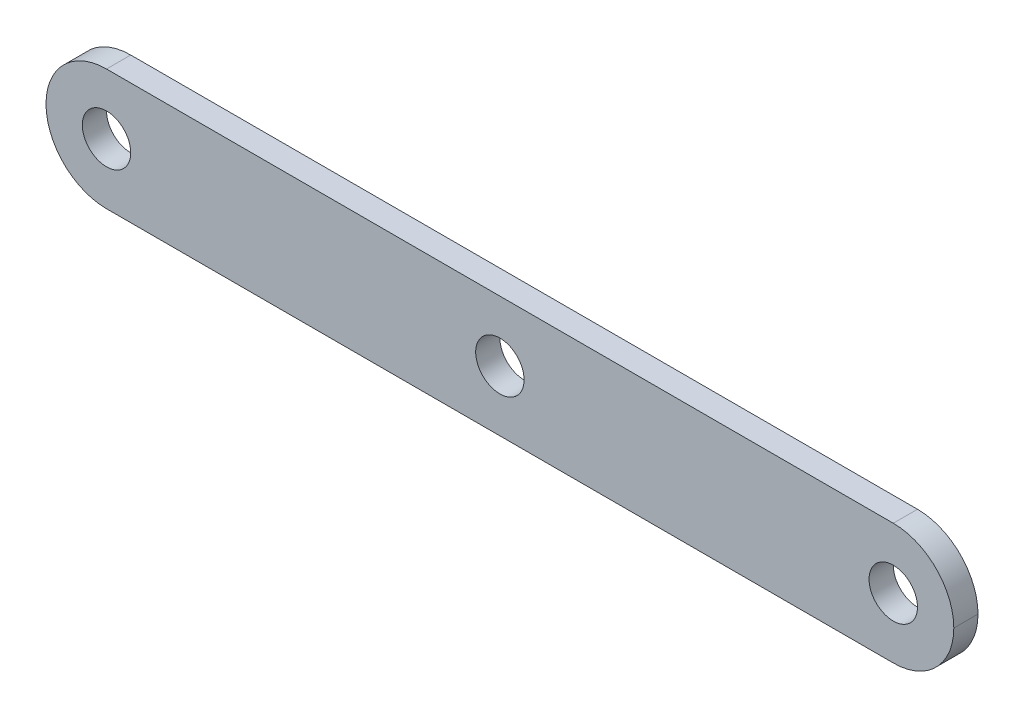
SolidWorks part; units mm, degrees
material "Thornel Mat VMA"
ref_plane "前视基准面" through (0, 0, 0) normal (0, 0, 1) x (1, 0, 0)
ref_plane "上视基准面" through (0, 0, 0) normal (0, 1, 0) x (1, 0, 0)
ref_plane "右视基准面" through (0, 0, 0) normal (1, 0, 0) x (0, 0, -1)
sketch "草图1" plane through (0, 0, 0) normal (0, 0, 1) x (1, 0, 0)
  line L1 (-37.5, -5) -> (37.5, -5)
  line L2 (-37.5, -5) -> (-37.5, 5)
  line L3 (-37.5, 5) -> (37.5, 5)
  line L4 (37.5, -5) -> (37.5, 5)
  line L5 (-37.5, -5) -> (37.5, 5) construction
  line L6 (-37.5, 5) -> (37.5, -5) construction
  point P0 (0, 0)
  dimension "D1" = 75
  dimension "D2" = 10
extrude "凸台-拉伸1" add sketch "草图1" along normal blind 2
fillet "圆角1" radius 5 4 edges at (37.5, -5, 1) (-37.5, -5, 1) (-37.5, 5, 1) (37.5, 5, 1)
sketch "草图3" plane through (0, 0, 2) normal (0, 0, 1) x (1, 0, 0)
  line L0 (0, 4.8774) -> (0, -3.8024) construction
  circle A0 centre (-32.5, 0) radius 2
  circle A1 centre (32.5, 0) radius 2
  circle A2 centre (0, 0) radius 2
  dimension "D1" = 4
  dimension "D2" = 4
extrude "切除-拉伸1" cut sketch "草图3" against normal blind 2
